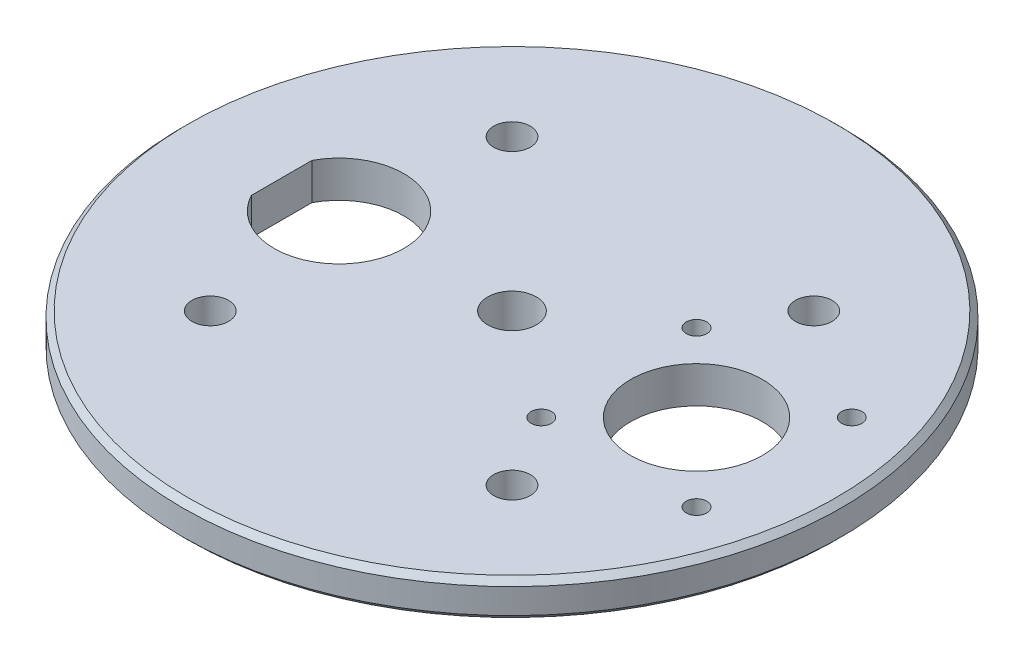
SolidWorks part; units mm, degrees
ref_plane "Front Plane" through (0, 0, 0) normal (0, 0, 1) x (1, 0, 0)
ref_plane "Top Plane" through (0, 0, 0) normal (0, 1, 0) x (1, 0, 0)
ref_plane "Right Plane" through (0, 0, 0) normal (1, 0, 0) x (0, 0, -1)
sketch "Sketch2" plane through (0, 0, 0) normal (0, 1, 0) x (1, 0, 0)
  circle A0 centre (0, 0) radius 57.15
  dimension "D1" = 114.3
extrude "Boss-Extrude1" add sketch "Sketch2" along normal blind 6.35 contours A0
sketch "Sketch6" plane through (0, 6.35, 0) normal (0, 1, 0) x (1, 0, 0)
  circle A0 centre (-26.1629, -26.1629) radius 3.175
  circle A1 centre (26.1629, -26.1629) radius 3.175
  circle A2 centre (-26.1629, 26.1631) radius 3.175
  circle A3 centre (26.1629, 26.1631) radius 3.175
  dimension "D1" = 6.35
  dimension "D2" = 74
  dimension "D3" = 26.1629
  dimension "D4" = 26.1629
  dimension "D5" = 26.1629
extrude "Cut-Extrude1" cut sketch "Sketch6" against normal up to next
sketch "Sketch7" plane through (0, 6.35, 0) normal (0, 1, 0) x (1, 0, 0)
  circle A0 centre (32, 0) radius 11.43
  circle A3 centre (18.54, -13.464) radius 1.778
  circle A4 centre (18.54, 13.46) radius 1.778
  circle A5 centre (45.46, 13.46) radius 1.778
  circle A6 centre (45.46, -13.464) radius 1.778
  dimension "D1" = 22.86
  dimension "D2" = 3.556
  dimension "D3" = 3.556
  dimension "D4" = 3.556
  dimension "D5" = 3.556
  dimension "D6" = 13.46
  dimension "D7" = 13.46
  dimension "D8" = 13.46
  dimension "D9" = 13.464
  dimension "D10" = 32
extrude "Cut-Extrude2" cut sketch "Sketch7" against normal through all
sketch "Sketch8" plane through (0, 6.35, 0) normal (0, 1, 0) x (1, 0, 0)
  line L0 (-39.95, 5.2498) -> (-39.95, -5.2498)
  circle A2 centre (0, 0) radius 4.2164
  arc A3 (-39.95, -5.2498) -> (-39.95, 5.2498) centre (-30, 0) ccw
  dimension "D1" = 9.95
  dimension "D3" = 8.4328
  dimension "D4" = 22.5
  dimension "D5" = 30
extrude "Cut-Extrude3" cut sketch "Sketch8" against normal through all
chamfer "Chamfer1" distance 1 angle 45 2 edges at (0, 0, 57.15) (0, 6.35, 57.15)
equation "\"width\"=26.1629"
equation "\"D4@Sketch6\"=\"width\""
equation "\"D3@Sketch6\"=\"width\""
equation "\"D5@Sketch6\"=\"width\""
